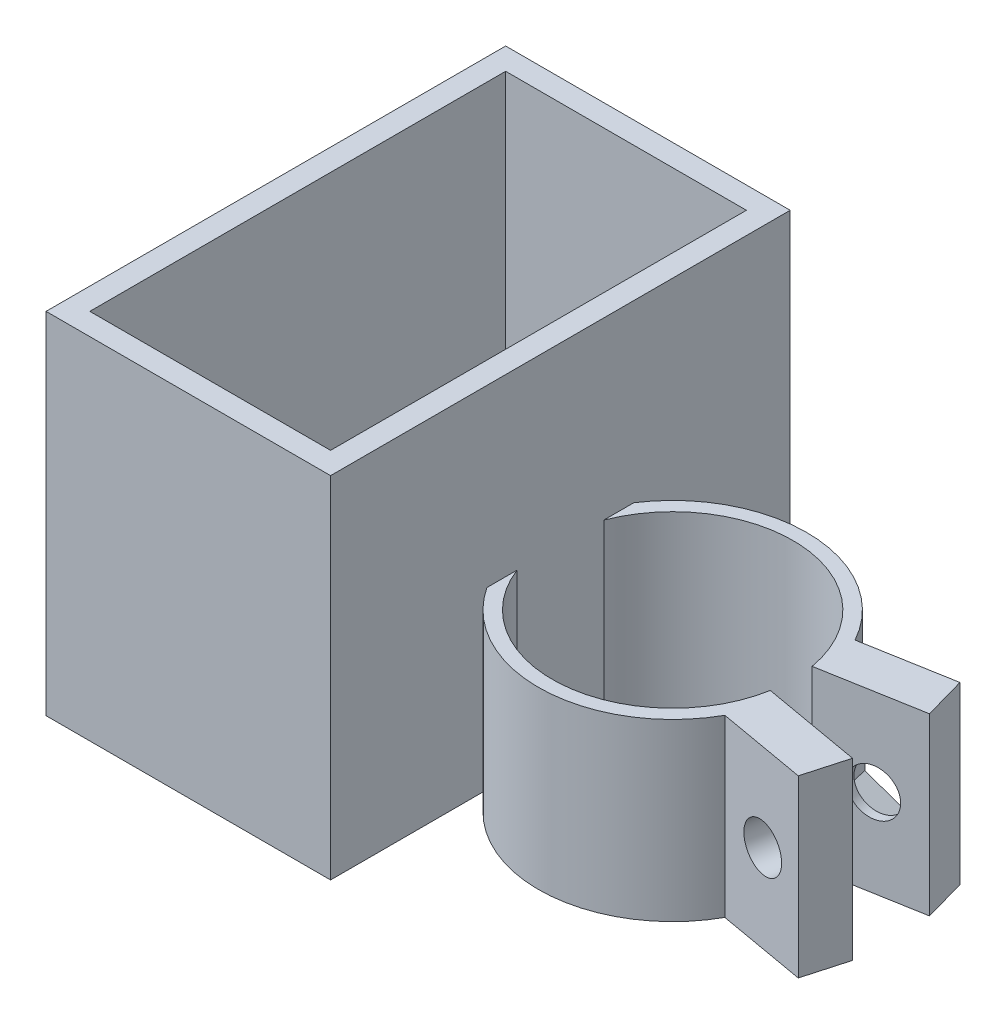
SolidWorks part; units mm, degrees
ref_plane "Front Plane" through (0, 0, 0) normal (0, 0, 1) x (1, 0, 0)
ref_plane "Top Plane" through (0, 0, 0) normal (0, 1, 0) x (1, 0, 0)
ref_plane "Right Plane" through (0, 0, 0) normal (1, 0, 0) x (0, 0, -1)
sketch "Sketch1" plane through (0, 0, 0) normal (0, 1, 0) x (1, 0, 0)
  line L1 (0, 0) -> (31.6739, -5.585)
  line L2 (0, 0) -> (31.6739, 5.585)
  line L3 (29.9477, -11.7286) -> (17.0153, -9.4482)
  line L4 (0, 0) -> (19.4625, 0) construction
  line L5 (29.9477, 11.7286) -> (17.0153, 9.4482)
  line L7 (31.6739, 5.585) -> (29.9477, 11.7286)
  line L8 (29.9477, -11.7286) -> (31.6739, -5.585)
  line L9 (17.0153, -9.4482) -> (19.1668, -3.3796)
  line L10 (19.1668, 3.3796) -> (17.0153, 9.4482)
  circle A0 centre (0, 0) radius 17.4625
  circle A1 centre (0, 0) radius 19.4625
  circle A2 centre (0, 0) radius 32.1625 construction
  dimension "D1" = 34.925
  dimension "D2" = 2
  dimension "D5" = 10
  dimension "D3" = 12.7
  dimension "D4" = 6.35
  dimension "D6" = 10
extrude "Boss-Extrude1" add sketch "Sketch1" along normal blind 25.4 contours L10 A1 L9 L1 A0 L2 | A1 L2 L7 L5 | A1 L3 L8 L1 | L9 A1 | L10 A1 region at (17.5742, 0, 6.2307) region at (18.1922, 0, 6.4498) region at (24.5347, 0, 7.5681) region at (18.1922, 0, -6.4498) region at (24.5347, 0, -7.5681)
sketch "Sketch3" plane through (-1.1027, 0, 6.2535) normal (-0.1736, 0, 0.9848) x (0.9848, 0, 0.1736)
  line L0 (31.5294, 25.4) -> (31.5294, 0) construction
  line L1 (31.5294, 25.4) -> (18.3975, 25.4) construction
  circle A0 centre (25.1794, 12.7) radius 3.3734
  dimension "D1" = 6.7469
  dimension "D2" = 6.35
  dimension "D3" = 12.7
sketch "Sketch4" plane through (-1.1027, 0, -6.2535) normal (-0.1736, 0, -0.9848) x (-0.9848, 0, 0.1736)
  line L0 (-31.5294, 25.4) -> (-31.5294, 0) construction
  line L1 (-31.5294, 25.4) -> (-18.3975, 25.4) construction
  circle A0 centre (-25.1794, 12.7) radius 3.3734
  point P6 (-22.813, 25.4)
  dimension "D3" = 6.7469
  dimension "D1" = 6.35
  dimension "D2" = 12.7
extrude "Cut-Extrude1" cut sketch "Sketch3" against normal up to next
extrude "Cut-Extrude2" cut sketch "Sketch4" against normal up to next
sketch "Sketch6" plane through (0, 0, 0) normal (0, -1, 0) x (1, 0, 0)
  line L0 (-19.4625, -30.1625) -> (-19.4625, 30.1625)
  line L1 (-16.2875, -33.3375) -> (-57.5625, -33.3375)
  line L2 (-16.2875, -33.3375) -> (-16.2875, 33.3375)
  line L3 (-16.2875, 33.3375) -> (-57.5625, 33.3375)
  line L4 (-57.5625, -33.3375) -> (-57.5625, 33.3375)
  line L5 (-19.4625, 30.1625) -> (-54.3875, 30.1625)
  line L6 (-54.3875, -30.1625) -> (-54.3875, 30.1625)
  line L7 (-19.4625, -30.1625) -> (-54.3875, -30.1625)
  arc A2 (17.0153, 9.4482) -> (17.0153, -9.4482) centre (0, 0) ccw construction
  point P8 (-19.4625, 0)
  dimension "D2" = 60.325
  dimension "D3" = 34.925
  dimension "D1" = 3.175
extrude "Boss-Extrude4" add sketch "Sketch6" against normal blind 50.8
sketch "Sketch7" plane through (0, 50.8, 0) normal (0, 1, 0) x (1, 0, 0)
  line L4 (-16.2875, -33.3375) -> (-16.2875, 33.3375)
  line L5 (-16.2875, 33.3375) -> (-57.5625, 33.3375)
  line L6 (-57.5625, 33.3375) -> (-57.5625, -33.3375)
  line L7 (-57.5625, -33.3375) -> (-16.2875, -33.3375)
  line L8 (-16.2875, -33.3375) -> (-16.2875, 33.3375)
  line L9 (-16.2875, 33.3375) -> (-57.5625, 33.3375)
  line L10 (-57.5625, 33.3375) -> (-57.5625, -33.3375)
  line L11 (-57.5625, -33.3375) -> (-16.2875, -33.3375)
  dimension "D1" = 0
sketch "Sketch8" plane through (-1.1027, 0, -6.2535) normal (-0.1736, 0, -0.9848) x (-0.9848, 0, 0.1736)
  line L1 (-19.6168, 9.4884) -> (-19.6168, 15.9116)
  line L2 (-19.6168, 15.9116) -> (-25.1794, 19.1231)
  line L3 (-25.1794, 19.1231) -> (-30.742, 15.9116)
  line L4 (-30.742, 15.9116) -> (-30.742, 9.4884)
  line L5 (-30.742, 9.4884) -> (-25.1794, 6.2769)
  line L6 (-25.1794, 6.2769) -> (-19.6168, 9.4884)
  circle A0 centre (-25.1794, 12.7) radius 5.5626 construction
  dimension "D1" = 11.1252
extrude "Cut-Extrude3" cut sketch "Sketch8" against normal blind 5.08 draft 4.3
sketch "Sketch9" plane through (0, 0, 0) normal (0, -1, 0) x (1, 0, 0)
  line L0 (-19.4625, -30.1625) -> (-19.4625, 30.1625) construction
  line L1 (-54.3875, -30.1625) -> (-19.4625, -30.1625) construction
  line L2 (-54.3875, 30.1625) -> (-54.3875, -30.1625) construction
  line L3 (-19.4625, 30.1625) -> (-54.3875, 30.1625) construction
  line L4 (-19.4625, -30.1625) -> (-19.4625, 30.1625)
  line L5 (-54.3875, -30.1625) -> (-19.4625, -30.1625)
  line L6 (-54.3875, 30.1625) -> (-54.3875, -30.1625)
  line L7 (-19.4625, 30.1625) -> (-54.3875, 30.1625)
extrude "Boss-Extrude6" add sketch "Sketch9" against normal blind 3.175
